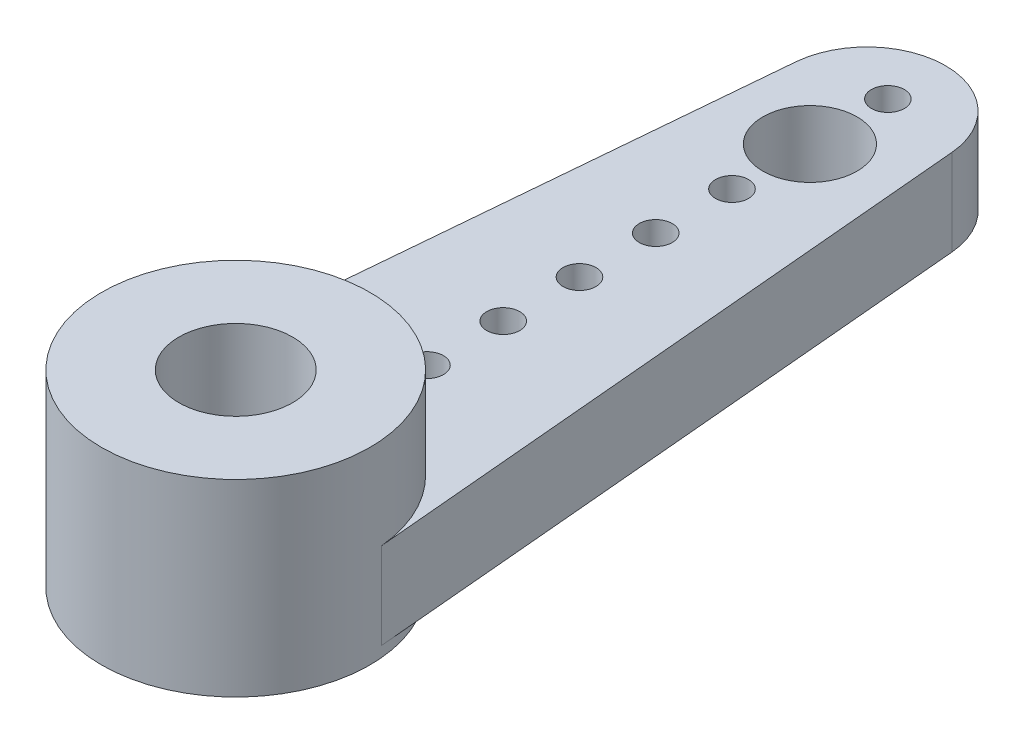
SolidWorks part; units mm, degrees
ref_plane "Front Plane" through (0, 0, 0) normal (0, 0, 1) x (1, 0, 0)
ref_plane "Top Plane" through (0, 0, 0) normal (0, 1, 0) x (1, 0, 0)
ref_plane "Right Plane" through (0, 0, 0) normal (1, 0, 0) x (0, 0, -1)
sketch "Sketch1" plane through (0, 0, 0) normal (0, 1, 0) x (1, 0, 0)
  line L0 (-3.4066, 0.302) -> (-1.9922, 16.2566)
  line L3 (1.9922, 16.2566) -> (3.4066, 0.302)
  line L4 (0, 0) -> (0, 16.08) construction
  line L5 (0, 18.08) -> (0, 16.08) construction
  line L6 (0, 0) -> (0, -3.42) construction
  arc A2 (-3.4066, 0.302) -> (3.4066, 0.302) centre (0, 0) ccw
  arc A3 (1.9922, 16.2566) -> (-1.9922, 16.2566) centre (0, 16.08) ccw
  dimension "D2" = 3.42
  dimension "D3" = 2
  dimension "D1" = 21.5
extrude "Boss-Extrude1" add sketch "Sketch1" along normal blind 2.2
sketch "Sketch2" plane through (0, 2.2, 0) normal (0, 1, 0) x (1, 0, 0)
  circle A0 centre (0, 0) radius 3.42
  arc A1 (-3.4066, 0.302) -> (3.4066, 0.302) centre (0, 0) ccw construction
extrude "Boss-Extrude2" add sketch "Sketch2" along normal blind 2.33
sketch "Sketch3" plane through (0, 4.53, 0) normal (0, 1, 0) x (1, 0, 0)
  circle A0 centre (0, 0) radius 2.06
  circle A1 centre (0, 0) radius 3.42 construction
  dimension "D1" = 1.36
sketch "Sketch4" plane through (0, 0, 0) normal (0, -1, 0) x (1, 0, 0)
  circle A2 centre (0, 0) radius 2.325
  dimension "D1" = 4.65
sketch "Sketch5" plane through (0, 0, 0) normal (0, 1, 0) x (1, 0, 0)
  circle A0 centre (0, 0) radius 1.16
  dimension "D1" = 2.32
sketch "Sketch6" plane through (0, 2.2, 0) normal (0, 1, 0) x (1, 0, 0)
  line L0 (0, 14.08) -> (0, 3.42) construction
  line L1 (0, 3.42) -> (0, -3.42) construction
  line L2 (0, 4.45) -> (2.0836, 4.45) construction
  line L3 (0, 5.29) -> (2.2632, 5.29) construction
  line L4 (0, 16.19) -> (2.6495, 16.19) construction
  line L5 (0.5439, -3.42) -> (4.0041, -3.42) construction
  line L6 (0, 12.64) -> (0, 14.625) construction
  line L7 (0, 16.61) -> (0, 14.625) construction
  line L8 (0, 12.22) -> (1.8481, 12.22) construction
  arc A0 (1.9922, 16.2566) -> (-1.9922, 16.2566) centre (0, 16.08) ccw construction
  arc A1 (3.4066, 0.302) -> (-3.4066, 0.302) centre (0, 0) ccw construction
  circle A2 centre (0, 4.87) radius 0.42
  circle A3 centre (0, 6.8125) radius 0.42
  circle A4 centre (0, 8.755) radius 0.42
  circle A5 centre (0, 10.6975) radius 0.42
  circle A6 centre (0, 12.64) radius 0.42
  circle A7 centre (0, 0) radius 3.42 construction
  arc A10 (-3.4066, 0.302) -> (3.4066, 0.302) centre (0, 0) ccw construction
  circle A11 centre (0, 14.625) radius 0.7
  circle A13 centre (0, 16.61) radius 0.42
  point P27 (0, 5.29)
  point P28 (0, 16.19)
  point P29 (0, 14.625)
  point P31 (0, 5.29)
  dimension "D4" = 19.61
  dimension "D5" = 1.4
  dimension "D6" = 15.64
  dimension "D2" = 7.87
  dimension "D3" = 10.9
  dimension "D1" = 5
extrude "Cut-Extrude5" cut sketch "Sketch6" against normal through all
mirror "Mirror1" [suppressed] about plane through (0, 0, 0) normal (0, 0, 1)
extrude "Cut-Extrude9" [suppressed] cut sketch "Sketch5" along normal through all
extrude "Cut-Extrude10" [suppressed] cut sketch "Sketch4" against normal blind 0.8
extrude "Cut-Extrude11" [suppressed] cut sketch "Sketch3" against normal blind 2.65
sketch "Sketch9" plane through (0, 0, 0) normal (0, -1, 0) x (1, 0, 0)
  circle A0 centre (0, 0) radius 3.42
  arc A1 (3.4066, -0.302) -> (-3.4066, -0.302) centre (0, 0) ccw construction
extrude "Boss-Extrude3" add sketch "Sketch9" along normal offset from surface (0.27 mm away) 4.8 up to face at (0, 4.53, 3.42)
sketch "Sketch10" plane through (0, -0.27, 0) normal (0, -1, 0) x (1, 0, 0)
  circle A0 centre (0, 0) radius 2.29
  dimension "D1" = 4.58
extrude "Cut-Extrude12" cut sketch "Sketch10" against normal blind 0.85
hole_wizard "M2.5 Clearance Hole2" positions "Sketch11" profile "Sketch12" hole size "M2.5" standard "ANSI Metric" end condition through all
sketch "Sketch11" plane through (0, 0.58, 0) normal (0, -1, 0) x (-1, 0, 0)
  point P0 (0, 0)
sketch "Sketch12" plane through (0, 0.58, 0) normal (1, 0, 0) x (0, 0, -1)
  line L0 (0, 0) -> (0, 3.95)
  line L1 (0, 3.95) -> (1.45, 3.95)
  line L2 (1.45, 3.95) -> (1.45, 0)
  line L5 (1.45, 0) -> (0, 0)
  line L11 (0, -6.35) -> (0, 107.95) construction
  dimension "Thru Hole Dia." = 2.9
  dimension "Thru Hole Depth" = 3.95
hole_wizard "M2 Clearance Hole1" positions "Sketch13" profile "Sketch14" hole size "M2" standard "ANSI Metric" end condition through all
sketch "Sketch13" plane through (0, 0, 0) normal (0, -1, 0) x (-1, 0, 0)
  point P0 (0, 14.625)
sketch "Sketch14" plane through (0, 0, -14.625) normal (1, 0, 0) x (0, 0, -1)
  line L0 (0, 0) -> (0, 4.53)
  line L1 (0, 4.53) -> (1.2, 4.53)
  line L2 (1.2, 4.53) -> (1.2, 0)
  line L5 (1.2, 0) -> (0, 0)
  line L11 (0, -6.35) -> (0, 107.95) construction
  dimension "Thru Hole Dia." = 2.4
  dimension "Thru Hole Depth" = 4.53
